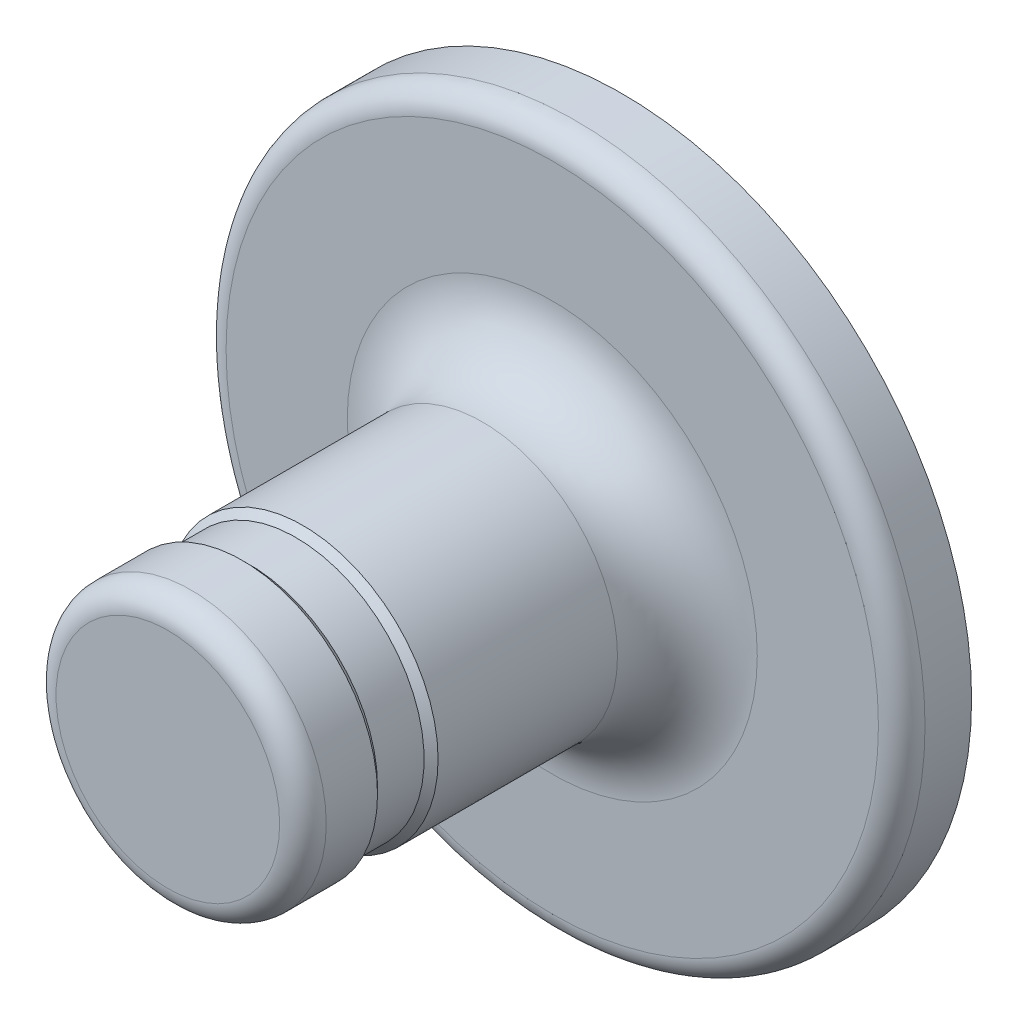
SolidWorks part; units mm, degrees
ref_plane "前视基准面" through (0, 0, 0) normal (0, 0, 1) x (1, 0, 0)
ref_plane "上视基准面" through (0, 0, 0) normal (0, 1, 0) x (1, 0, 0)
ref_plane "右视基准面" through (0, 0, 0) normal (1, 0, 0) x (0, 0, -1)
other "Configuration Table"
sketch "草图1" plane through (0, 0, 0) normal (0, 0, 1) x (1, 0, 0)
  circle A0 centre (0, 0) radius 15
  dimension "D1" = 30
extrude "凸台-拉伸1" add sketch "草图1" along normal blind 3
sketch "草图2" plane through (0, 0, 3) normal (0, 0, 1) x (1, 0, 0)
  circle A0 centre (0, 0) radius 5.8
  dimension "D1" = 11.6
extrude "凸台-拉伸2" add sketch "草图2" along normal blind 16.5
fillet "圆角1" radius 3 1 edges at (5.8, 0, 3)
fillet "圆角2" radius 1 1 edges at (15, 0, 3)
fillet "圆角3" radius 1 1 edges at (5.8, 0, 19.5)
ref_plane "基准面1" through (0, 0, 13) normal (0, 0, -1) x (-1, 0, 0)
sketch "草图3" plane through (0, 0, 13) normal (0, 0, -1) x (-1, 0, 0)
  circle A0 centre (0, 0) radius 5.5
  circle A1 centre (0, 0) radius 6
  dimension "D1" = 12
  dimension "D2" = 11
extrude "切除-拉伸1" cut sketch "草图3" against normal blind 4
chamfer "倒角1" distance 1 angle 45 2 edges at (-5.5, 0, 13) (-5.5, 0, 17)
